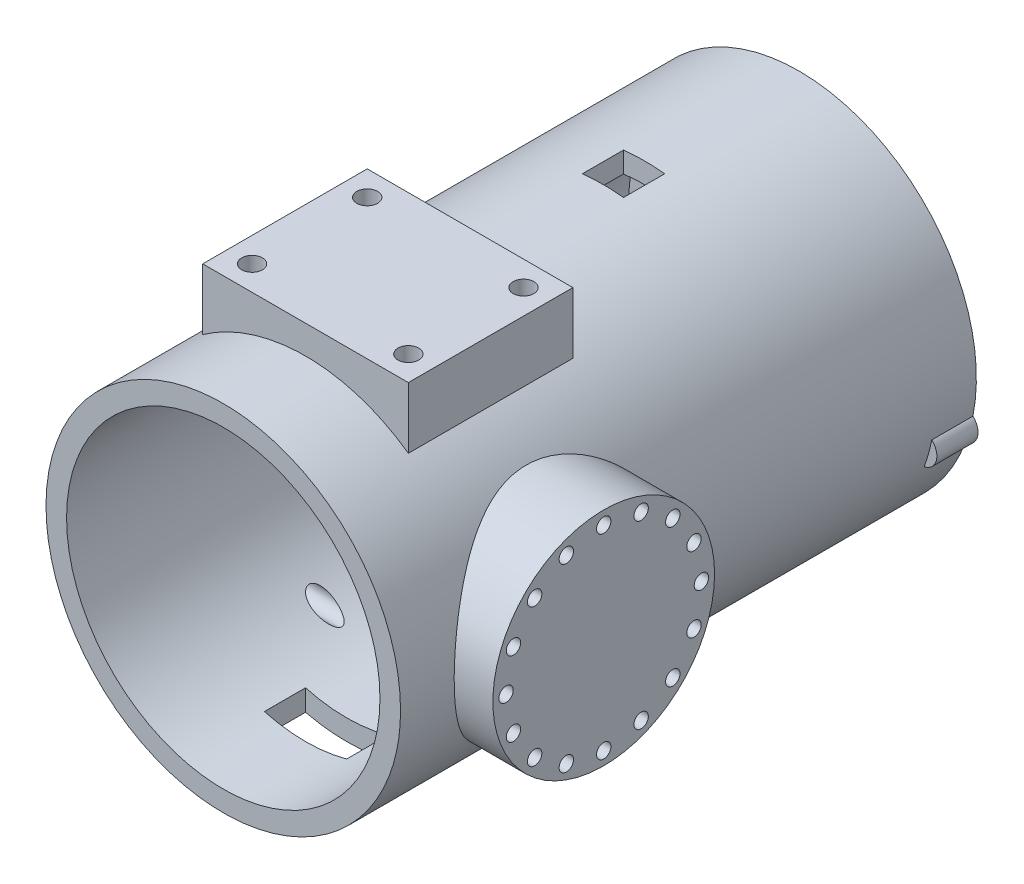
SolidWorks part; units mm, degrees
other "Markup1"
sketch "Sketch14" plane through (-43.1, 43.1, 140) normal (-0.1765, 0.0048, 0.9843) x (0.9842, -0.0149, 0.1765)
other "Markup2"
sketch "Sketch23" plane through (45.1, -43.1, 140) normal (0.9491, -0.0629, 0.3087) x (0.311, 0.031, -0.9499)
ref_plane "Front Plane" through (0, 0, 0) normal (0, 0, 1) x (1, 0, 0)
ref_plane "Top Plane" through (0, 0, 0) normal (0, 1, 0) x (1, 0, 0)
ref_plane "Right Plane" through (0, 0, 0) normal (1, 0, 0) x (0, 0, -1)
sketch "Sketch1" plane through (0, 0, 0) normal (0, 0, 1) x (1, 0, 0)
  circle A1 centre (0, 0) radius 43.1
  dimension "D1" = 86.2
extrude "Main Body" add sketch "Sketch1" along normal blind 140
ref_plane "Plane1" through (0, 43.1, 0) normal (0, 1, 0) x (1, 0, 0)
sketch "Sketch34" [suppressed] plane through (0, 43.1, 0) normal (0, 1, 0) x (1, 0, 0)
  line L6 (-5, -13) -> (5, -13)
  line L8 (-5, -13) -> (-5, -3)
  line L9 (-5, -3) -> (5, -3)
  line L10 (5, -13) -> (5, -3)
  line L11 (-5, -13) -> (5, -3) construction
  line L12 (-5, -3) -> (5, -13) construction
  point P0 (0, -8)
  dimension "D1" = 8
  dimension "D2" = 10
  dimension "D3" = 10
sketch "Sketch6" plane through (0, 43.1, 0) normal (0, 1, 0) x (1, 0, 0)
  line L2 (-5, -47.7) -> (5, -47.7)
  line L3 (-5, -47.7) -> (-5, -37.7)
  line L4 (-5, -37.7) -> (5, -37.7)
  line L5 (5, -47.7) -> (5, -37.7)
  line L6 (-5, -47.7) -> (5, -37.7) construction
  line L7 (-5, -37.7) -> (5, -47.7) construction
  point P2 (0, -42.7)
  dimension "D2" = 10
  dimension "D1" = 42.7
  dimension "D3" = 10
extrude "Cut-Extrude3" cut sketch "Sketch6" against normal through all
ref_plane "Plane2" through (52.5, 0, 0) normal (1, 0, 0) x (0, 0, -1)
sketch "Sketch8" plane through (52.5, 0, 0) normal (1, 0, 0) x (0, 0, -1)
  circle A0 centre (-100, 0) radius 26.95
  dimension "D1" = 53.9
  dimension "D2" = 100
extrude "Boss-Extrude2" add sketch "Sketch8" against normal blind 20
mirror "Mirror1" [suppressed] about plane through (0, 0, 0) normal (1, 0, 0)
ref_plane "Plane3" through (0, 50, 0) normal (0, 1, 0) x (1, 0, 0)
sketch "Sketch33" plane through (0, 50, 0) normal (0, 1, 0) x (1, 0, 0)
  line L1 (-25, -120) -> (25, -120)
  line L2 (-25, -120) -> (-25, -80)
  line L3 (-25, -80) -> (25, -80)
  line L4 (25, -120) -> (25, -80)
  line L5 (-25, -120) -> (25, -80) construction
  line L6 (-25, -80) -> (25, -120) construction
  point P0 (0, -100)
  dimension "D1" = 100
  dimension "D2" = 40
  dimension "D3" = 50
extrude "Boss-Extrude11" add sketch "Sketch33" against normal blind 22
sketch "Sketch35" plane through (0, 50, 0) normal (0, 1, 0) x (1, 0, 0)
  line L0 (-25, -120) -> (-25, -80) construction
  line L1 (25, -120) -> (25, -80) construction
  line L2 (25, -80) -> (-25, -80) construction
  line L3 (-25, -120) -> (25, -120) construction
  circle A0 centre (-19, -86) radius 2.525
  circle A1 centre (19, -86) radius 2.525
  circle A2 centre (-19, -114) radius 2.525
  circle A3 centre (19, -114) radius 2.525
  dimension "D1" = 5.05
  dimension "D2" = 6
  dimension "D3" = 6
  dimension "D4" = 6
  dimension "D5" = 6
extrude "Cut-Extrude14" cut sketch "Sketch35" against normal blind 4
sketch "Sketch5" plane through (0, 0, 140) normal (0, 0, 1) x (1, 0, 0)
  circle A0 centre (0, 0) radius 31.75
  dimension "D1" = 63.5
extrude "Hole 1" cut sketch "Sketch5" against normal through all
sketch "Sketch10" plane through (0, 0, 0) normal (0, 1, 0) x (1, 0, 0)
  line L0 (43.1, 0) -> (-43.1, 0) construction
  line L1 (-10, -120) -> (10, -120)
  line L2 (-10, -120) -> (-10, -110)
  line L3 (-10, -110) -> (10, -110)
  line L4 (10, -120) -> (10, -110)
  line L5 (-10, -120) -> (10, -110) construction
  line L6 (-10, -110) -> (10, -120) construction
  point P0 (0, -115)
  point P7 (-10, -115)
  dimension "D1" = 110
  dimension "D2" = 10
  dimension "D3" = 20
extrude "Motor Wire Hole" cut sketch "Sketch10" against normal through all
sketch "Sketch27" plane through (0, 0, 0) normal (1, 0, 0) x (0, 0, -1)
  line L1 (-100, -36.5) -> (-60, -36.5)
  line L2 (-100, -36.5) -> (-100, -27.5)
  line L3 (-100, -27.5) -> (-60, -27.5)
  line L4 (-60, -36.5) -> (-60, -27.5)
  dimension "D1" = 60
  dimension "D2" = 27.5
  dimension "D3" = 40
  dimension "D4" = 9
extrude "Boss-Extrude9" add sketch "Sketch27" along normal blind 33 and the other way blind 33
sketch "Sketch11" plane through (0, 0, 0) normal (1, 0, 0) x (0, 0, -1)
  circle A0 centre (-65, -32) radius 2.5
  circle A1 centre (-95, -32) radius 2.5
  dimension "D3" = 5
  dimension "D1" = 65
  dimension "D2" = 32
  dimension "D4" = 30
extrude "Cut-Extrude6" cut sketch "Sketch11" against normal through all both and the other way through all
sketch "Sketch28" plane through (-33, 0, 0) normal (-1, 0, 0) x (0, 0, 1)
  line L0 (62.9793, -28.5) -> (67.0207, -28.5)
  line L1 (67.0207, -28.5) -> (69.0415, -32)
  line L2 (69.0415, -32) -> (67.0207, -35.5)
  line L3 (67.0207, -35.5) -> (62.9793, -35.5)
  line L4 (62.9793, -35.5) -> (60.9585, -32)
  line L6 (60.9585, -32) -> (62.9793, -28.5)
  line L7 (92.9793, -28.5) -> (97.0207, -28.5)
  line L8 (97.0207, -28.5) -> (99.0415, -32)
  line L9 (99.0415, -32) -> (97.0207, -35.5)
  line L10 (97.0207, -35.5) -> (92.9793, -35.5)
  line L11 (92.9793, -35.5) -> (90.9585, -32)
  line L12 (90.9585, -32) -> (92.9793, -28.5)
  circle A0 centre (65, -32) radius 3.5 construction
  circle A1 centre (65, -32) radius 2.5 construction
  circle A2 centre (95, -32) radius 3.5 construction
  circle A3 centre (95, -32) radius 2.5 construction
  dimension "D1" = 7
  dimension "D2" = 7
extrude "Cut-Extrude7" cut sketch "Sketch28" against normal blind 3
sketch "Sketch29" plane through (33, 0, 0) normal (1, 0, 0) x (0, 0, -1)
  circle A0 centre (-95, -32) radius 3.5
  circle A1 centre (-65, -32) radius 3.5
  dimension "D1" = 7
extrude "Cut-Extrude8" cut sketch "Sketch29" against normal blind 4
sketch "Sketch2" plane through (0, 0, 140) normal (0, 0, 1) x (1, 0, 0)
  circle A0 centre (0, 0) radius 38.1
  dimension "D1" = 76.2
extrude "Cut-Extrude5" cut sketch "Sketch2" against normal blind 135
sketch "Sketch9" plane through (0, 0, 5) normal (0, 0, 1) x (1, 0, 0)
  circle A0 centre (0, 0) radius 38.1
  circle A1 centre (0, 0) radius 36.44
  dimension "D1" = 76.2
  dimension "D2" = 1.66
extrude "Boss-Extrude3" add sketch "Sketch9" along normal blind 10
extrude "Cut-Extrude13" [suppressed] cut sketch "Sketch34" against normal blind 15
sketch "Sketch30" plane through (52.5, 0, 0) normal (1, 0, 0) x (0, 0, -1)
  line L0 (-100, 23.75) -> (-100, 0) construction
  circle A0 centre (-100, 0) radius 23.75 construction
  circle A1 centre (-100, 23.75) radius 1.75
  circle A2 centre (-90.9113, 21.9421) radius 1.75
  circle A3 centre (-83.2062, 16.7938) radius 1.75
  circle A4 centre (-78.0579, 9.0887) radius 1.75
  circle A5 centre (-76.25, 0) radius 1.75
  circle A6 centre (-78.0579, -9.0887) radius 1.75
  circle A7 centre (-83.2062, -16.7938) radius 1.75
  circle A8 centre (-90.9113, -21.9421) radius 1.75
  circle A9 centre (-100, -23.75) radius 1.75
  circle A10 centre (-109.0887, -21.9421) radius 1.75
  circle A11 centre (-116.7938, -16.7938) radius 1.75
  circle A12 centre (-121.9421, -9.0887) radius 1.75
  circle A13 centre (-123.75, 0) radius 1.75
  circle A14 centre (-121.9421, 9.0887) radius 1.75
  circle A15 centre (-116.7938, 16.7938) radius 1.75
  circle A16 centre (-109.0887, 21.9421) radius 1.75
  point P38 (-100, 0)
  dimension "D1" = 47.5
  dimension "D2" = 3.5
  dimension "D3" = 16
extrude "Cut-Extrude9" cut sketch "Sketch30" against normal up to surface (22.7083 mm away) up to face at (38.1, 0, 15)
sketch "Sketch31" plane through (52.5, 0, 0) normal (1, 0, 0) x (0, 0, -1)
  line L0 (0, -43.1) -> (0, 43.1) construction
  line L1 (0, -15) -> (-10, -15)
  line L2 (0, -15) -> (0, -7.5)
  line L3 (0, -7.5) -> (-10, -7.5)
  line L4 (-10, -15) -> (-10, -7.5)
  dimension "D1" = 15
  dimension "D2" = 7.5
  dimension "D3" = 10
extrude "Boss-Extrude10" add sketch "Sketch31" against normal up to body from offset 9 offset against normal yes
sketch "Sketch32" plane through (0, 0, 0) normal (0, 0, -1) x (-1, 0, 0)
  line L0 (-43.5, -11.25) -> (-29.6901, -11.25) construction
  line L1 (-43.5, -15) -> (-43.5, -7.5) construction
  line L3 (-42.4424, -7.5) -> (-43.5, -7.5) construction
  line L5 (-43.5, -15) -> (-43.5, -7.5)
  line L6 (-43.5, -7.5) -> (-42.4424, -7.5)
  circle A0 centre (0, 0) radius 31.75 construction
  arc A2 (-40.4056, -15) -> (-42.4424, -7.5) centre (0, 0) ccw construction
  arc A3 (-40.4056, -15) -> (-42.2658, -8.4385) centre (-39.6806, -11.25) cw
  arc A4 (-42.2658, -8.4385) -> (-42.4424, -7.5) centre (0, 0) cw
  line M3 (-42.4424, -7.5) -> (-43.5, -7.5)
  line M4 (-43.5, -7.5) -> (-43.5, -15)
  line M5 (-43.5, -15) -> (-40.4056, -15)
extrude "Cut-Extrude10" cut sketch "Sketch32" against normal up to surface (10 mm away) contours M4 M3 | L5 M5 region at (43.0347, -8.5479, 0) region at (42.7123, -14.1508, 0) up to face at (42.5043, -11.2615, 10)
